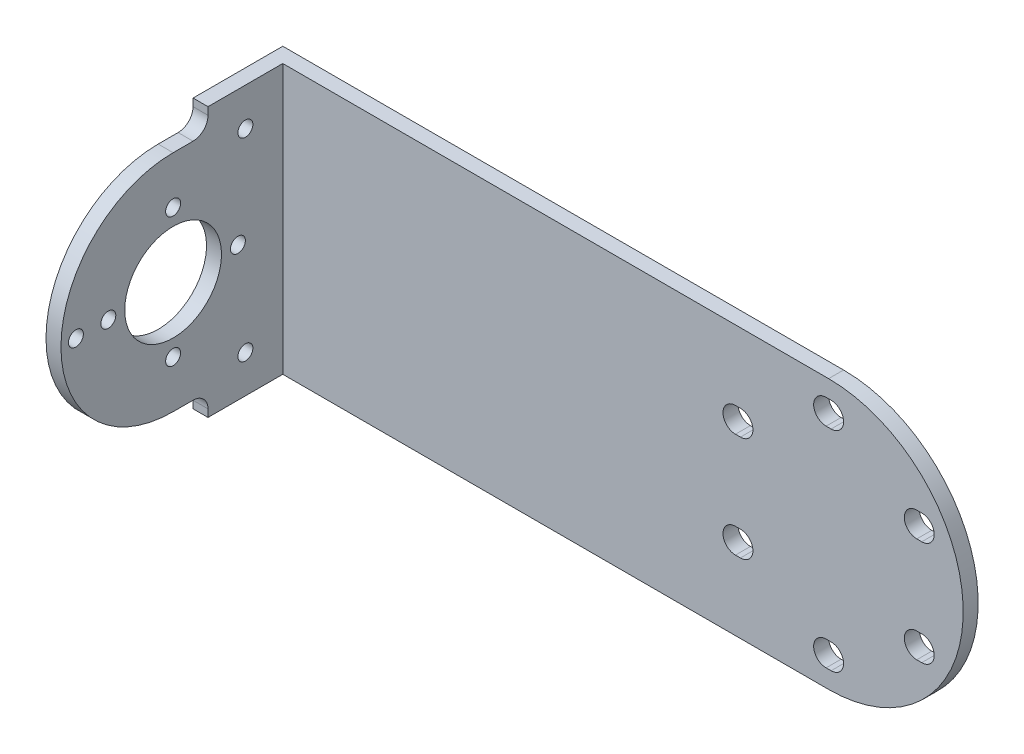
SolidWorks part; units mm, degrees
material "1060 Alloy"
ref_plane "Front Plane" through (0, 0, 0) normal (0, 0, 1) x (1, 0, 0)
ref_plane "Top Plane" through (0, 0, 0) normal (0, 1, 0) x (1, 0, 0)
ref_plane "Right Plane" through (0, 0, 0) normal (1, 0, 0) x (0, 0, -1)
sketch "Sketch1" plane through (0, 0, 0) normal (0, 0, 1) x (1, 0, 0)
  line L0 (-112.5, 27) -> (0, 27)
  line L1 (-112.5, -27) -> (0, -27)
  line L2 (17.6865, 10.5) -> (18.6865, 10.5) construction
  line L3 (-112.5, 27) -> (-112.5, -27)
  line L4 (-113, -28) -> (-113, 28) construction
  line L7 (17.6865, 13) -> (18.6865, 13)
  line L8 (17.6865, 8) -> (18.6865, 8)
  line L9 (17.6865, -10.5) -> (18.6865, -10.5) construction
  line L10 (17.6865, -8) -> (18.6865, -8)
  line L11 (17.6865, -13) -> (18.6865, -13)
  line L12 (-0.5, -21) -> (0.5, -21) construction
  line L13 (-0.5, -18.5) -> (0.5, -18.5)
  line L14 (-0.5, -23.5) -> (0.5, -23.5)
  line L15 (-18.6865, -10.5) -> (-17.6865, -10.5) construction
  line L16 (-18.6865, -8) -> (-17.6865, -8)
  line L17 (-18.6865, -13) -> (-17.6865, -13)
  line L18 (-17.6865, 10.5) -> (-18.6865, 10.5) construction
  line L19 (-17.6865, 8) -> (-18.6865, 8)
  line L20 (-17.6865, 13) -> (-18.6865, 13)
  line L21 (0.5, 21) -> (-0.5, 21) construction
  line L22 (0.5, 18.5) -> (-0.5, 18.5)
  line L23 (0.5, 23.5) -> (-0.5, 23.5)
  arc A1 (17.6865, 13) -> (17.6865, 8) centre (17.6865, 10.5) ccw
  circle A2 centre (18.1865, -10.5) radius 2.5 construction
  circle A3 centre (0, -21) radius 2.5 construction
  circle A4 centre (-18.1865, -10.5) radius 2.5 construction
  circle A5 centre (-18.1865, 10.5) radius 2.5 construction
  circle A6 centre (0, 21) radius 2.5 construction
  arc A7 (0, -27) -> (0, 27) centre (0, 0) ccw
  arc A8 (22.4, 16.8) -> (0, 28) centre (0, 0) ccw construction
  arc A11 (18.6865, 8) -> (18.6865, 13) centre (18.6865, 10.5) ccw
  circle A12 centre (18.1865, 10.5) radius 2.5 construction
  arc A13 (17.6865, -8) -> (17.6865, -13) centre (17.6865, -10.5) ccw
  arc A14 (18.6865, -13) -> (18.6865, -8) centre (18.6865, -10.5) ccw
  arc A15 (-0.5, -18.5) -> (-0.5, -23.5) centre (-0.5, -21) ccw
  arc A16 (0.5, -23.5) -> (0.5, -18.5) centre (0.5, -21) ccw
  arc A17 (-18.6865, -8) -> (-18.6865, -13) centre (-18.6865, -10.5) ccw
  arc A18 (-17.6865, -13) -> (-17.6865, -8) centre (-17.6865, -10.5) ccw
  arc A19 (-17.6865, 8) -> (-17.6865, 13) centre (-17.6865, 10.5) ccw
  arc A20 (-18.6865, 13) -> (-18.6865, 8) centre (-18.6865, 10.5) ccw
  arc A21 (0.5, 18.5) -> (0.5, 23.5) centre (0.5, 21) ccw
  arc A22 (-0.5, 23.5) -> (-0.5, 18.5) centre (-0.5, 21) ccw
  circle A23 centre (18.1865, -10.5) radius 2.5 construction
  circle A24 centre (0, -21) radius 2.5 construction
  circle A25 centre (-18.1865, -10.5) radius 2.5 construction
  circle A26 centre (-18.1865, 10.5) radius 2.5 construction
  circle A27 centre (0, 21) radius 2.5 construction
  point P3 (18.1865, 10.5)
  point P18 (0, 0)
  point P33 (18.1865, -10.5)
  point P41 (0, -21)
  point P48 (-18.1865, -10.5)
  point P56 (-18.1865, 10.5)
  point P62 (0, 21)
  dimension "D2" = 1
  dimension "D3" = 0.5
  dimension "D1" = 1
extrude "Boss-Extrude1" add sketch "Sketch1" along normal blind 3 contours A7 L0 L3 L1 region at (-46.4625, 0, 0)
sketch "Sketch2" plane through (-112.5, 0, 0) normal (-1, 0, 0) x (0, 0, 1)
  line L0 (3, -27) -> (18, -27)
  line L1 (18, -27) -> (18, -25.5)
  line L2 (21, -22.5) -> (25, -22.5)
  line L3 (0, 0) -> (41.5, 0) construction
  line L4 (3, 27) -> (18, 27)
  line L5 (18, 27) -> (18, 25.5)
  line L6 (21, 22.5) -> (25, 22.5)
  line L7 (25, 9.7) -> (25, 16.3) construction
  line L8 (47.5, 0) -> (41.5, 0) construction
  line L9 (15.134, -13.2254) -> (5.866, -25.6494) construction
  line L10 (15.134, -13.2254) -> (44.134, 25.6494) construction
  circle A0 centre (25, 0) radius 32 construction
  circle A2 centre (10.5, -19.4374) radius 1.5
  circle A3 centre (25, 13) radius 1.5
  circle A4 centre (25, 13) radius 1.5 construction
  circle A5 centre (38, 0) radius 1.5
  circle A6 centre (25, -13) radius 1.5
  circle A7 centre (12, 0) radius 1.5
  circle A8 centre (25, 0) radius 9.7
  circle A10 centre (25, 0) radius 9.5 construction
  arc A11 (18, -25.5) -> (21, -22.5) centre (21, -25.5) cw
  arc A12 (18, 25.5) -> (21, 22.5) centre (21, 25.5) ccw
  circle A13 centre (10.5, 19.4374) radius 1.5
  arc A14 (25, -22.5) -> (25, 22.5) centre (25, 0) ccw
  circle A16 centre (44.5, 0) radius 1.5
  circle A19 centre (25, 0) radius 16.5 construction
  circle A21 centre (25, 0) radius 32 construction
  arc A22 (22, -22.2991) -> (22, 22.2991) centre (25, 0) ccw construction
  point P15 (25, 13)
  point P34 (25, 0)
  point P50 (44.5, 0)
  point P58 (10.5, -19.4374)
  point P62 (10.5, -27)
  line M7 (3, -27) -> (3, 27)
  dimension "D1" = 6
  dimension "D4" = 0.2
  dimension "D5" = 3
  dimension "D7" = 3
  dimension "D2" = 15
  dimension "D3" = 4
extrude "Boss-Extrude2" add sketch "Sketch2" against normal blind 3 contours L3 A7 A5 L5 L4 A3 M7 | L3 L0 L1 A5 A7 A6 M7 region at (-112.5, 0, 3.6997)
